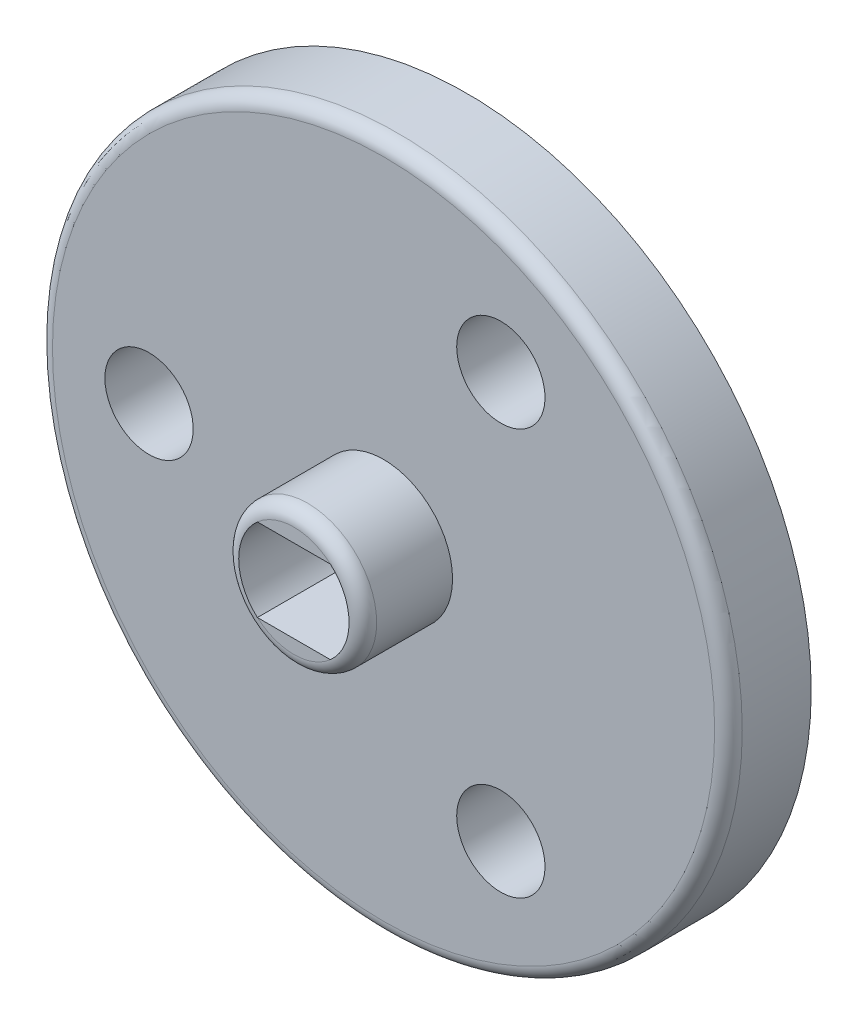
SolidWorks part; units mm, degrees
ref_plane "Ebene vorne" through (0, 0, 0) normal (0, 0, 1) x (1, 0, 0)
ref_plane "Ebene oben" through (0, 0, 0) normal (0, 1, 0) x (1, 0, 0)
ref_plane "Ebene rechts" through (0, 0, 0) normal (1, 0, 0) x (0, 0, -1)
sketch "Skizze1" plane through (0, 0, 0) normal (1, 0, 0) x (0, 0, -1)
  line L1 (96.5, 25) -> (96.5, 0) construction
  line L2 (90.5, 25) -> (90.5, 0) construction
  line L3 (0, 25) -> (99, 25) construction
  line L5 (96.5, 25) -> (96.5, 0)
  line L6 (90.5, 25) -> (90.5, 5)
  line L7 (90.5, 25) -> (96.5, 25)
  line L8 (84, 4) -> (84, 0) construction
  line L10 (84, 4) -> (84, 0)
  line L12 (0, 0) -> (99, 0) construction
  line L13 (84, 0) -> (96.5, 0)
  line L14 (84, 5) -> (84, 4) construction
  line L15 (90.5, 5) -> (84, 5) construction
  line L16 (84, 5) -> (84, 4)
  line L17 (90.5, 5) -> (84, 5)
revolve "Rotation1" add sketch "Skizze1" angle 360 about L13
sketch "Skizze2" plane through (0, 0, -96.5) normal (0, 0, -1) x (-1, 0, 0)
  line L0 (0, 0) -> (25, 0) construction
  line L1 (0, 0) -> (-450, 0) construction
  line L2 (2.6458, 3) -> (-2.6458, 3) construction
  line L3 (0, 0) -> (4, 0)
  line L4 (0, 0) -> (-4, 0)
  line L5 (2.6458, 3) -> (-2.6458, 3)
  arc A1 (-2.6458, 3) -> (-4, 0) centre (0, 0) ccw construction
  arc A2 (4, 0) -> (2.6458, 3) centre (0, 0) ccw construction
  arc A3 (-2.6458, 3) -> (-4, 0) centre (0, 0) ccw
  arc A4 (4, 0) -> (2.6458, 3) centre (0, 0) ccw
extrude "Schnitt-Linear austragen1" cut sketch "Skizze2" against normal through all
mirror "Spiegeln1" about plane through (0, 0, -84) normal (0, -1, 0) of "Schnitt-Linear austragen1"
sketch "Skizze3" plane through (0, 0, -96.5) normal (0, 0, -1) x (-1, 0, 0)
  circle A0 centre (0, 0) radius 17 construction
  point P7 (17, 0)
hole_wizard "Ø6.4 (6.4) Durchmesser Bohrung1" positions "Skizze3" profile "Skizze4" hole size "Ø6.4" standard "DIN"
sketch "Skizze4" plane through (-17, 0, -96.5) normal (1, 0, 0) x (0, 1, 0)
  line L0 (0, 0) -> (0, 10.4228)
  line L1 (0, 10.4228) -> (3.2, 8.5)
  line L2 (3.2, 8.5) -> (3.2, 0)
  line L5 (3.2, 0) -> (0, 0)
  line L10 (0, 10.4228) -> (-3.2, 8.5) construction
  line L11 (0, -6.35) -> (0, 107.95) construction
  dimension "Bohrerdurchmesser" = 6.4
  dimension "Bohrungstiefe" = 8.5
  dimension "Spitzenwinkel" = 118
pattern_circular "Kreismuster1" count 3 over 360 of "Ø6.4 (6.4) Durchmesser Bohrung1" reverse direction yes
fillet "Verrundung1" radius 1 2 edges at (5, 0, -84) (25, 0, -90.5)
